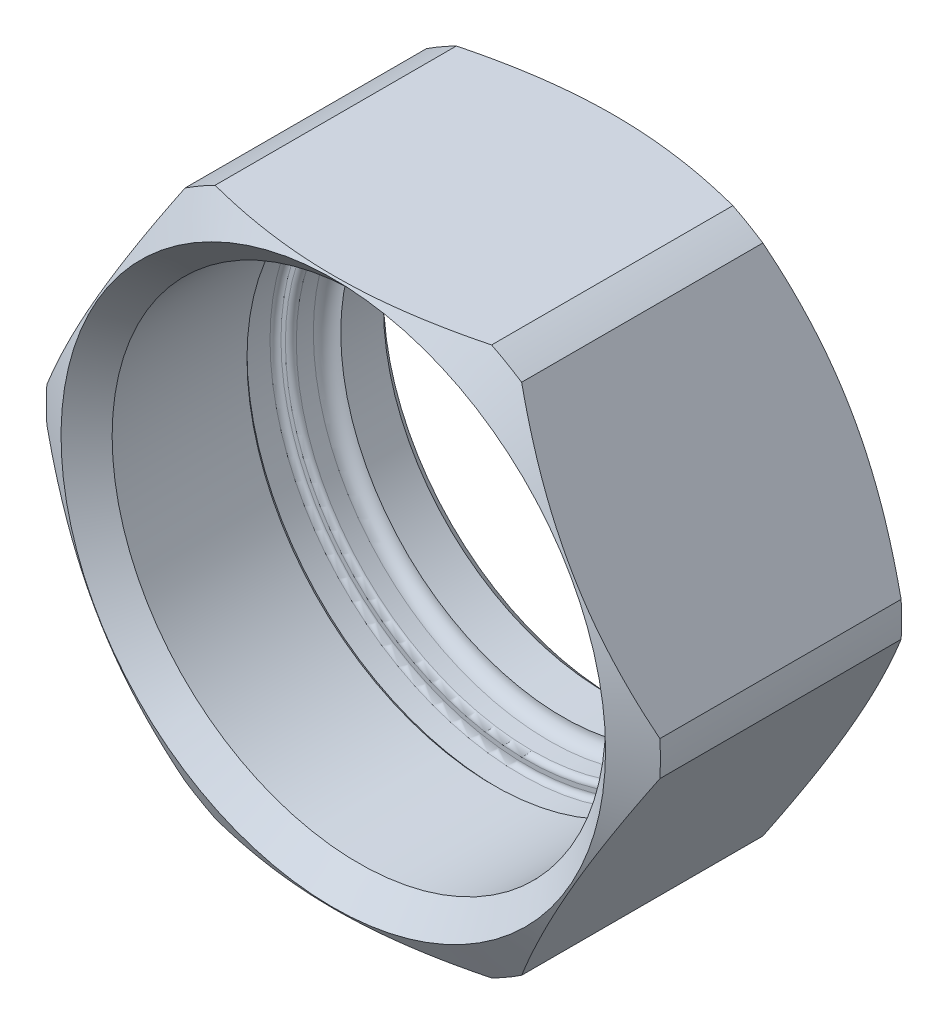
SolidWorks part; units mm, degrees
material "3.0205 (EN-AW 1200)"
ref_plane "Спереди" through (0, 0, 0) normal (0, 0, 1) x (1, 0, 0)
ref_plane "Сверху" through (0, 0, 0) normal (0, 1, 0) x (1, 0, 0)
ref_plane "Справа" through (0, 0, 0) normal (1, 0, 0) x (0, 0, -1)
sketch "Эскиз1" plane through (0, 0, 0) normal (0, 0, 1) x (1, 0, 0)
  line L1 (28.8675, 0) -> (14.4338, 25)
  line L2 (14.4338, 25) -> (-14.4338, 25)
  line L3 (-14.4338, 25) -> (-28.8675, 0)
  line L4 (-28.8675, 0) -> (-14.4338, -25)
  line L5 (-14.4338, -25) -> (14.4338, -25)
  line L6 (14.4338, -25) -> (28.8675, 0)
  circle A0 centre (0, 0) radius 25 construction
  dimension "D1" = 50
extrude "Бобышка-Вытянуть1" add sketch "Эскиз1" against normal blind 26
sketch "Эскиз4" plane through (0, 0, 0) normal (0, 1, 0) x (1, 0, 0)
  line L0 (-28.8675, 26) -> (-28.8675, 23.5)
  line L1 (-28.8675, 26) -> (-28.8675, 0) construction
  line L2 (-28.8675, 23.5) -> (-24.5374, 26)
  line L3 (-14.4338, 26) -> (-28.8675, 26) construction
  line L4 (-24.5374, 26) -> (-28.8675, 26)
  line L5 (-28.8675, 0) -> (-28.8675, 2.5)
  line L6 (-28.8675, 2.5) -> (-24.5374, 0)
  line L7 (-14.4338, 0) -> (-28.8675, 0) construction
  line L8 (-24.5374, 0) -> (-28.8675, 0)
  line L9 (0, 0) -> (0, 28.5342) construction
  dimension "D1" = 30
  dimension "D2" = 30
  dimension "D3" = 2.5
  dimension "D4" = 2.5
revolve "Вырез-Повернуть1" cut sketch "Эскиз4" angle 360 about L9
sketch "Эскиз5" plane through (0, 0, 0) normal (0, 1, 0) x (1, 0, 0)
  line L0 (0, 0) -> (-22.5, 0)
  line L1 (-24.5374, 0) -> (24.5374, 0) construction
  line L2 (-22.5, 0) -> (-22.5, 14.8)
  line L3 (-22.5, 14.8) -> (-22.9, 15.2)
  line L4 (-22.9, 15.2) -> (-22.9, 17.8)
  line L5 (-22.9, 17.8) -> (-21.5, 17.8)
  line L6 (-21.5, 17.8) -> (-21.5, 21.1)
  line L7 (-21.5, 21.1) -> (-20.25, 21.1)
  line L8 (-20.25, 21.1) -> (-20.25, 26)
  line L9 (24.5374, 26) -> (-24.5374, 26) construction
  line L10 (-20.25, 26) -> (0, 26)
  line L11 (0, 26) -> (0, 0)
  dimension "D1" = 45
  dimension "D2" = 22.5
  dimension "D3" = 3
  dimension "D4" = 3.3
  dimension "D5" = 17.8
  dimension "D6" = 22.9
  dimension "D7" = 21.5
  dimension "D8" = 20.25
revolve "Вырез-Повернуть2" cut sketch "Эскиз5" angle 360 about L11
fillet "Скругление1" radius 1.25 1 edges at (-21.5, 0, -21.1)
thread "Резьба2" [suppressed] pitch 1.5 start angle 0, offset 0, length 15.5, pitch 1.5, diameter 45
ref_plane "Плоскость4" through (-22.5, 0, 0) normal (0, -1, 0) x (-1, 0, 0)
sketch "Профиль резьбы4" plane through (-22.5, 0, 0) normal (0, -1, 0) x (-1, 0, 0)
  line L0 (0, 0) -> (0, 1.5) construction
  line L11 (0, 0) -> (0, 1.3125)
  line L12 (0, 1.3125) -> (-0.8119, 0.8437)
  line L13 (-0.8119, 0.8437) -> (-0.8119, 0.4687)
  line L15 (-0.8119, 0.4687) -> (0, 0)
  line L17 (-0.8119, 0.6562) -> (0, 0.6562) construction
  point P2 (0, 0)
  dimension "Pitch" = 1.5
  dimension "Profile_Angle" = 60
  dimension "Profile_Land" = 0.375
  dimension "Profile_Height" = 0.8119
sketch "Эскиз17" plane through (0, 0, 0) normal (0, 0, 1) x (1, 0, 0)
  circle A0 centre (0, 0) radius 22.5 construction
  circle A1 centre (0, 0) radius 22.5
  circle A2 centre (0, 0) radius 21.415
  dimension "D1" = 42.83
extrude "Бобышка-Вытянуть2" add sketch "Эскиз17" along normal blind 1.5 separate body
chamfer "Фаска1" distance 1.5 angle 45 1 edges at (21.415, 0, 1.5)
sketch "Эскиз18" plane through (0, 0, 0) normal (0, 0, 1) x (1, 0, 0)
  circle A0 centre (0, 0) radius 28.8675
extrude "Вырез-Вытянуть2" cut sketch "Эскиз18" along normal through all
fillet "Скругление2" radius 0.5 2 edges at (-21.5, 0, -17.8) (-22.9, 0, -17.8)
chamfer "Фаска2" distance 1 angle 45 1 edges at (-20.25, 0, -26)
sketch "Эскиз19" plane through (0, 0, -26) normal (0, 0, -1) x (-1, 0, 0)
  circle A0 centre (0, 0) radius 28
  dimension "D1" = 56
extrude "Вырез-Вытянуть4" cut sketch "Эскиз19" against normal through all flip side to cut
chamfer "Фаска3" distance 2.5 angle 45 1 edges at (-22.5, 0, 0)
